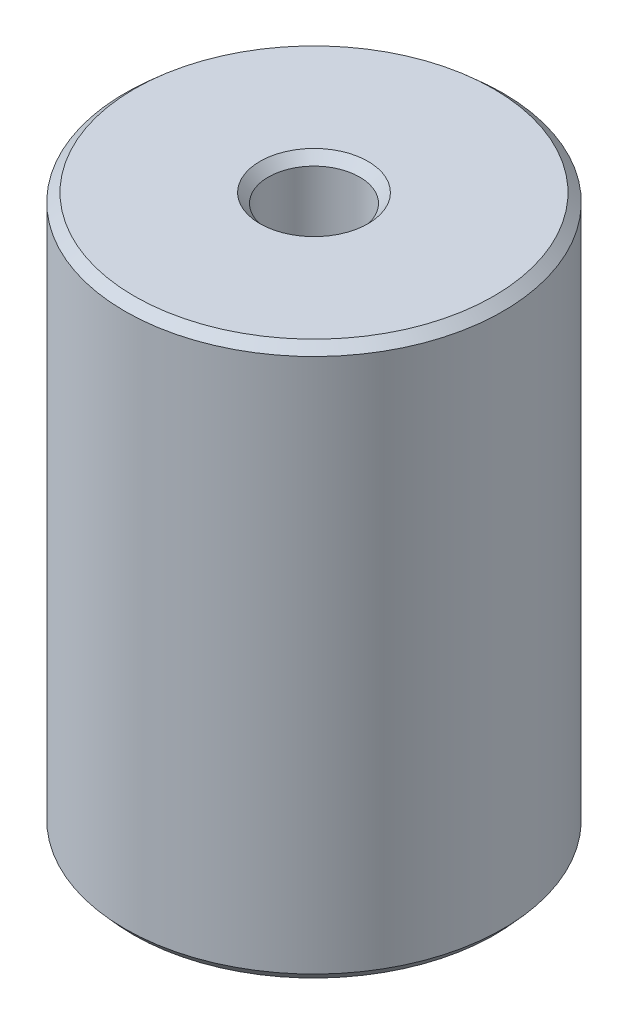
SolidWorks part; units mm, degrees
ref_plane "Front Plane" through (0, 0, 0) normal (0, 0, 1) x (1, 0, 0)
ref_plane "Top Plane" through (0, 0, 0) normal (0, 1, 0) x (1, 0, 0)
ref_plane "Right Plane" through (0, 0, 0) normal (1, 0, 0) x (0, 0, -1)
sketch "Sketch1" plane through (0, 0, 0) normal (0, 1, 0) x (1, 0, 0)
  circle A0 centre (0, 0) radius 5
  dimension "SLEEVE_OD" = 10
extrude "Boss-Extrude1" add sketch "Sketch1" along normal blind 14.6188
sketch "Sketch2" plane through (0, 0, 0) normal (0, 1, 0) x (1, 0, 0)
  circle A0 centre (0, 0) radius 1.2077
  dimension "BORE_D" = 2.4154
extrude "Cut-Extrude1" cut sketch "Sketch2" along normal through all
chamfer "Chamfer1" distance 0.2221 angle 48.168 4 edges at (0, 14.6188, 1.2077) (0, 0, 1.2077) (0, 0, 5) (0, 14.6188, 5) first distance on face at (0, 14.6188, 1.2077) first distance on face at (0, 0, 1.2077) first distance on face at (0, 14.6188, 5)
